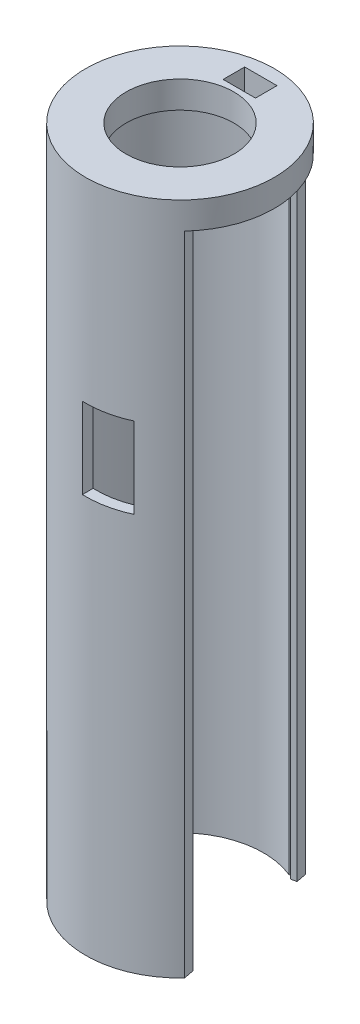
SolidWorks part; units mm, degrees
ref_plane "Front Plane" through (0, 0, 0) normal (0, 0, 1) x (1, 0, 0)
ref_plane "Top Plane" through (0, 0, 0) normal (0, 1, 0) x (1, 0, 0)
ref_plane "Right Plane" through (0, 0, 0) normal (1, 0, 0) x (0, 0, -1)
sketch "Sketch12" plane through (0, 0, 0) normal (0, 1, 0) x (1, 0, 0)
  line L0 (7.7396, 13.9749) -> (7.3665, 15.874)
  line L1 (7.7396, 13.9749) -> (6.7581, 13.7836)
  line L2 (6.7581, 13.7836) -> (6.6184, 14.4945)
  line L3 (6.6184, 14.4945) -> (5.8646, 14.3477)
  line L4 (11.438, -10.2388) -> (12.4196, -10.0475)
  line L5 (12.4196, -10.0475) -> (12.7892, -11.9451)
  line L6 (11.438, -10.2388) -> (11.5754, -10.9501)
  line L7 (11.5754, -10.9501) -> (10.8217, -11.0969)
  line L8 (5.418, 16.6402) -> (5.7049, 15.1678) construction
  line L9 (5.7049, 15.1678) -> (7.4386, 15.5072) construction
  line L10 (10.9814, -11.9171) -> (11.2683, -13.3894) construction
  line L11 (10.9814, -11.9171) -> (12.7158, -11.5808) construction
  arc A0 (7.3665, 15.874) -> (12.7892, -11.9451) centre (0, 0) ccw
  arc A2 (5.8646, 14.3477) -> (10.8217, -11.0969) centre (0, 0) ccw
  dimension "D1" = 15.5
  dimension "D2" = 17.5
  dimension "D3" = 1.8992
  dimension "D4" = 0.7538
  dimension "D5" = 0.7538
  dimension "D6" = 1.9332
extrude "Boss-Extrude1" add sketch "Sketch12" along normal blind 120
sketch "Sketch13" plane through (0, 120, 0) normal (0, 1, 0) x (1, 0, 0)
  circle A0 centre (0, 0) radius 17.5
  circle A1 centre (0, 0) radius 10
  dimension "D1" = 20
  dimension "D2" = 35
extrude "Boss-Extrude3" add sketch "Sketch13" along normal blind 5
sketch "Sketch16" plane through (0, 125, 0) normal (0, 1, 0) x (1, 0, 0)
  line L0 (0, 0) -> (0, 17.5) construction
  line L2 (3, 11) -> (-3, 11)
  line L3 (3, 11) -> (3, 15)
  line L4 (3, 15) -> (-3, 15)
  line L5 (-3, 11) -> (-3, 15)
  line L6 (3, 11) -> (-3, 15) construction
  line L7 (3, 15) -> (-3, 11) construction
  circle A0 centre (0, 0) radius 17.5 construction
  point P6 (0, 13)
  dimension "D1" = 4
  dimension "D2" = 6
  dimension "D3" = 11
extrude "Cut-Extrude1" cut sketch "Sketch16" against normal blind 5
sketch "Sketch17" plane through (0, 0, 0) normal (0, 0, 1) x (1, 0, 0)
  line L1 (-0.6234, 88.7322) -> (7.3766, 88.7322)
  line L2 (-0.6234, 88.7322) -> (-0.6234, 73.7322)
  line L3 (-0.6234, 73.7322) -> (7.3766, 73.7322)
  line L4 (7.3766, 88.7322) -> (7.3766, 73.7322)
  line L5 (-0.6234, 88.7322) -> (7.3766, 73.7322) construction
  line L6 (-0.6234, 73.7322) -> (7.3766, 88.7322) construction
  point P0 (3.3766, 81.2322)
  dimension "D1" = 8
  dimension "D2" = 15
extrude "Cut-Extrude2" cut sketch "Sketch17" along normal blind 150
sketch "Sketch18" plane through (0, 0, 0) normal (1, 0, 0) x (0, 0, -1)
  circle A0 centre (0.165, 93.7642) radius 8
  dimension "D1" = 16
extrude "Cut-Extrude5" cut sketch "Sketch18" against normal blind 20 contours A0
